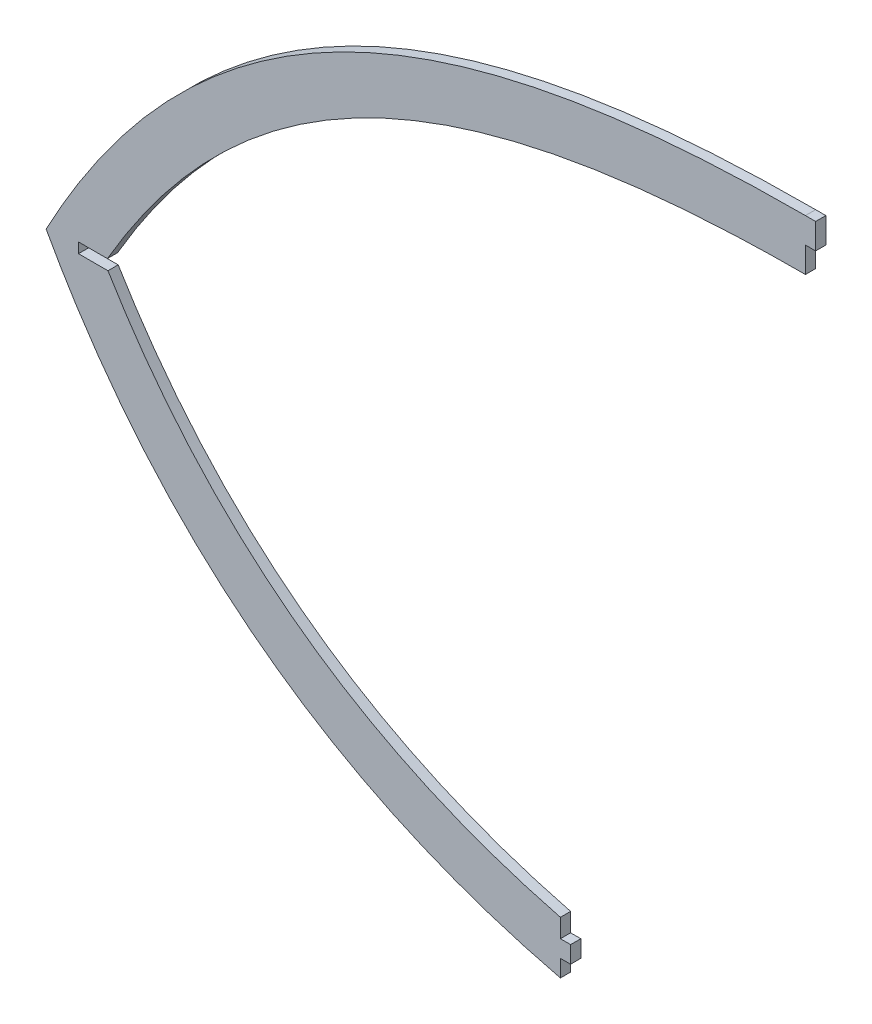
SolidWorks part; units mm, degrees
material "birch 3mm plywood"
ref_plane "Front" through (0, 0, 0) normal (0, 0, 1) x (1, 0, 0)
ref_plane "Top" through (0, 0, 0) normal (0, 1, 0) x (1, 0, 0)
ref_plane "Right" through (0, 0, 0) normal (1, 0, 0) x (0, 0, -1)
sketch "Sketch1" plane through (0, 0, 0) normal (0, 0, 1) x (1, 0, 0)
  line L1 (-83, 160.5) -> (-83, -69.5) construction
  line L2 (-83, 153) -> (-80, 153)
  line L4 (-155, -69.5) -> (-155, -64.5)
  line L8 (-155, 43.3771) -> (-155, -69.5) construction
  line L9 (-155, -64.5) -> (-152, -64.5)
  line L10 (-152, -69.5) -> (-152, 43.3771) construction
  line L12 (-152, -64.5) -> (-152, -59.5)
  line L13 (-152, -59.5) -> (-155, -59.5)
  line L14 (-155, -59.5) -> (-155, -54.0482)
  line L15 (-288.0952, 47) -> (-296.5952, 47)
  line L16 (-83, 47) -> (-305.0917, 47) construction
  line L17 (-296.5952, 47) -> (-296.5952, 44)
  line L18 (-305.0917, 44) -> (-83, 44) construction
  line L19 (-296.5952, 44) -> (-287.9228, 44)
  line L20 (-83, 160.5) -> (-83, 150.5) construction
  line L21 (-83, 160.5) -> (-80, 160.5)
  line L22 (-80, 160.5) -> (-80, 153)
  line L23 (-83, 153) -> (-83, 145.5)
  parabola Q0 (-155, -69.5) -> (-306.0893, 45.5) focus (-179.0197, 57.3821) apex (-244.7409, -27.552) construction
  parabola Q1 (-155, -69.5) -> (-306.0893, 45.5) focus (-179.0197, 57.3821) apex (-244.7409, -27.552)
  spline S0 degree 3 poles (1891.2416, 272.7748) (-235.7671, -531.3158) (-630.9131, 1514.8652) (-226.857, -1948.382) knots -3.131082 -3.131082 -3.131082 -3.131082 3.356894 3.356894 3.356894 3.356894 only from (-83, 160.5) to (-306.0893, 45.5) construction
  spline S1 degree 3 poles (-83, 160.5) (-186.6749, 160.5) (-259.8996, 132.37) (-306.0893, 45.5) knots 0 0 0 0 1 1 1 1
  spline S2 degree 1 poles (-151.4967, -54.9148) (-288.8909, 45.6217) knots 0 0 1 1 construction
  spline S3 degree 1 poles (-83, 145.5) (-288.8909, 45.6217) knots 0 0 1 1 construction
  spline S4 degree 3 poles (-151.4967, -54.9148) (-153.3988, -54.458) (-157.2086, -53.4983) (-164.6601, -51.4419) (-173.7484, -48.594) (-184.2693, -44.7413) (-197.7998, -39.024) (-213.7896, -30.7928) (-231.5494, -19.1756) (-247.9291, -5.7971) (-260.462, 6.8492) (-269.8307, 17.8876) (-276.5289, 26.6314) (-281.8406, 34.3147) (-285.9211, 40.691) (-287.9161, 43.9748) (-288.8909, 45.6217) knots 0.497669 0.497669 0.497669 0.497669 0.497806 0.497943 0.498217 0.498491 0.498765 0.499314 0.499862 0.500411 0.500959 0.501233 0.501508 0.501782 0.501919 0.502056 0.502056 0.502056 0.502056 only from (-155, -54.0482) to (-287.9228, 44)
  spline S5 degree 3 poles (-288.8909, 45.6217) (-288.2118, 46.8068) (-286.8274, 49.1771) (-284.0331, 53.7809) (-280.4563, 59.3452) (-276.0412, 65.7051) (-269.9863, 73.7792) (-262.1032, 83.1283) (-252.1296, 93.2247) (-241.6235, 102.2655) (-226.87, 112.9967) (-206.9505, 124.0773) (-184.8372, 132.3478) (-165.7316, 137.4023) (-150.6813, 140.4388) (-134.8993, 142.7481) (-121.1337, 144.0897) (-109.751, 144.8283) (-101.0301, 145.2187) (-93.6051, 145.4111) (-87.5802, 145.4874) (-84.523, 145.5) (-83, 145.5) knots 0 0 0 0 0.015161 0.030323 0.060645 0.090968 0.12129 0.181936 0.242581 0.303226 0.363871 0.485162 0.606452 0.667098 0.727743 0.788388 0.849033 0.879356 0.909679 0.940001 0.955163 0.970324 0.970324 0.970324 0.970324 only from (-288.0952, 47) to (-83, 145.5)
  dimension "D2" = 7.5
  dimension "D3" = 5
  dimension "D4" = 5
  dimension "D5" = 8.5
  dimension "D1" = 15
extrude "Boss-Extrude1" add sketch "Sketch1" along normal mid plane 3 contours S1 Q1 L4 L9 L12 L13 L14 S4 L19 L17 L15 S5 L23 L2 L22 L21
